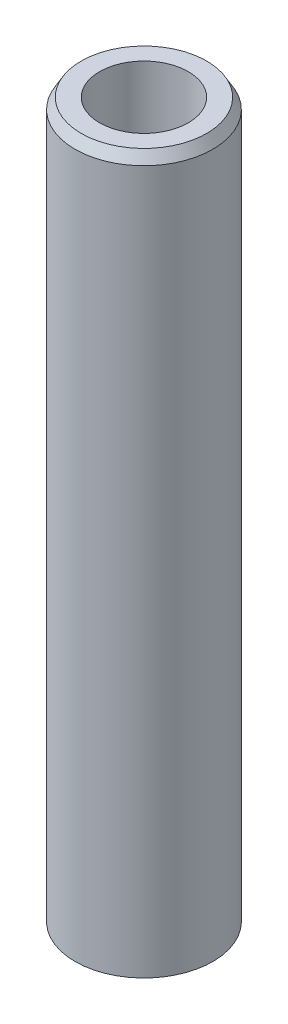
SolidWorks part; units mm, degrees
ref_plane "Front Plane" through (0, 0, 0) normal (0, 0, 1) x (1, 0, 0)
ref_plane "Top Plane" through (0, 0, 0) normal (0, 1, 0) x (1, 0, 0)
ref_plane "Right Plane" through (0, 0, 0) normal (1, 0, 0) x (0, 0, -1)
sketch "Sketch1" plane through (0, 0, 0) normal (0, 1, 0) x (1, 0, 0)
  circle A0 centre (0, 0) radius 37.5
  dimension "SHAFT_OD" = 75
extrude "Boss-Extrude1" add sketch "Sketch1" along normal blind 392.0361
sketch "Sketch2" plane through (0, 0, 0) normal (0, 1, 0) x (1, 0, 0)
  circle A0 centre (0, 0) radius 24.1433
  dimension "BORE_D" = 48.2866
extrude "Cut-Extrude1" cut sketch "Sketch2" along normal through all
chamfer "Chamfer1" distance 5.7989 angle 30 2 edges at (0, 392.0361, 37.5) (0, 0, 37.5) first distance on face at (0, 392.0361, 37.5) first distance on face at (0, 0, 24.1433)
